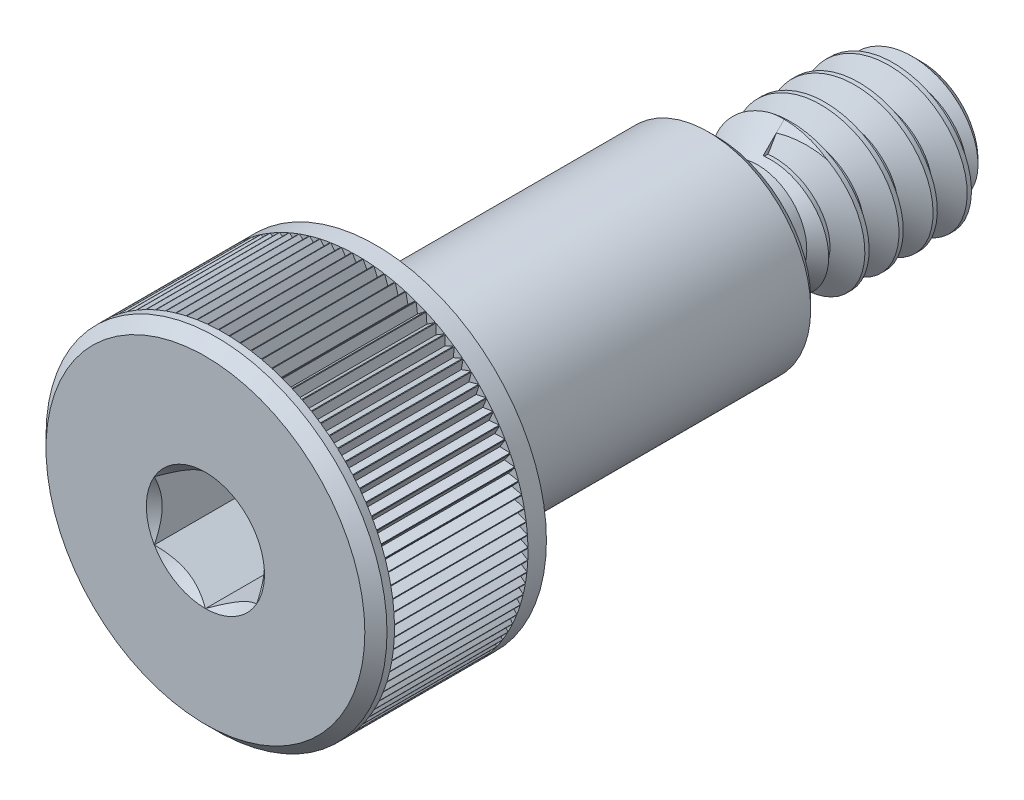
SolidWorks part; units mm, degrees
other "DetailItem1"
other "DetailItem2"
other "DetailItem5"
other "DetailItem6"
ref_plane "Front" through (0, 0, 0) normal (0, 0, 1) x (1, 0, 0)
ref_plane "Top" through (0, 0, 0) normal (0, 1, 0) x (1, 0, 0)
ref_plane "Right" through (0, 0, 0) normal (1, 0, 0) x (0, 0, -1)
sketch "Sketch1" plane through (0, 0, 0) normal (1, 0, 0) x (0, 0, -1)
  line L0 (0, 3.9687) -> (3.9687, 3.9688) construction
  line L1 (3.9687, 3.9688) -> (3.9687, 2.1828) construction
  line L2 (4.9609, 2.3812) -> (11.9062, 2.3812) construction
  line L3 (4.9609, -2.3812) -> (11.9063, -2.3813) construction
  line L4 (11.9063, 1.7526) -> (16.6688, 1.7526) construction
  line L5 (16.6688, 1.7526) -> (16.6688, 0) construction
  line L6 (11.9063, 0) -> (0, 0) construction
  line L7 (0, 0) -> (0, 3.9687) construction
  line L8 (0, 3.9687) -> (0, -3.9688) construction
  line L9 (16.6688, 1.7526) -> (16.6688, -1.7526) construction
  line L10 (11.9062, 2.3812) -> (11.9063, -2.3813) construction
  line L11 (16.6688, -1.7526) -> (14.991, -1.7526) construction
  line L12 (11.9062, 2.3812) -> (11.9063, 0) construction
  line L13 (3.9687, 2.1828) -> (4.7625, 2.1828) construction
  line L14 (4.7625, 2.1828) -> (4.9609, 2.3812) construction
  line L15 (16.6688, 0) -> (11.9063, 0) construction
  line L16 (4.7625, -2.1828) -> (4.9609, -2.3812) construction
  line L17 (3.9688, -2.1828) -> (4.7625, -2.1828) construction
  line L18 (0, -3.9688) -> (3.9688, -3.9688) construction
  line L19 (3.9688, -3.9688) -> (3.9688, -2.1828) construction
  line L20 (16.6688, 2.3813) -> (15.4781, 2.3813) construction
  line L21 (16.6688, -2.3812) -> (15.4781, -2.3812) construction
  line L22 (16.6688, 0) -> (21.4313, 0) construction
  line L23 (7.9375, 0) -> (7.9375, 3.9688) construction
  line L24 (16.6688, -2.3812) -> (16.6688, 2.3813) construction
  line L25 (0, -1.1906) -> (0, 1.1906) construction
  line L26 (16.6191, 1.8385) -> (17.4129, 1.8385) construction
  line L27 (17.4129, 1.8385) -> (17.016, 1.1511) construction
  line L28 (17.016, 1.1511) -> (16.6191, 1.8385) construction
  line L29 (17.016, 1.1511) -> (17.016, 1.237) construction
  line L30 (17.016, 1.8385) -> (17.016, 1.7526) construction
  line L31 (17.3633, 1.7526) -> (16.6688, 1.7526) construction
  line L32 (16.9664, 1.237) -> (17.0656, 1.237) construction
  line L33 (17.016, 1.7956) -> (17.3881, 1.7956) construction
  line L34 (17.016, 1.7956) -> (16.6439, 1.7956) construction
  line L35 (4.9609, 2.3812) -> (4.9609, -2.3812) construction
  line L36 (11.7078, 2.3813) -> (11.9063, 2.1828) construction
  line L37 (11.7078, 2.3813) -> (11.7078, 0) construction
  point P2 (4.1672, 0)
  point P8 (15.4781, -1.7526)
  point P12 (11.9063, 0)
  point P15 (11.7078, 0)
  point P31 (4.5442, 0)
  point P32 (11.3308, 0)
  point P34 (16.6688, 0)
  point P37 (0, 0)
  dimension "Head Dia" = 7.9375
  dimension "Head Ht" = 3.9688
  dimension "Thread Lg" = 4.7625
  dimension "Thread Dia" = 3.5052
  dimension "Shoulder Dia" = 4.7625
  dimension "D1" = 1.1906
  dimension "D2" = 1.6778
  dimension "D3" = 135
  dimension "D4" = 0.7937
  dimension "D5" = 0.1984
  dimension "D6" = 3.9688
  dimension "D7" = 7.5406
  dimension "D8" = 6.7866
  dimension "Hex" = 2.3813
  dimension "Pitch" = 0.7937
  dimension "D9" = 0.0992
  dimension "Shoulder Lg" = 7.9375
  dimension "D10" = 45
sketch "Sketch13" plane through (0, 0, 0) normal (1, 0, 0) x (0, 0, -1)
  line L0 (0, 0) -> (0, 3.9687)
  line L1 (0, 3.9687) -> (3.9687, 3.9688)
  line L2 (3.9687, 3.9688) -> (3.9687, 2.1828)
  line L3 (3.9687, 2.1828) -> (4.7625, 2.1828)
  line L4 (11.9062, 0) -> (11.9062, 2.1828)
  line L5 (4.7625, 2.1828) -> (4.9609, 2.3812)
  line L7 (11.9062, 2.3812) -> (11.9062, 0) construction
  line L8 (11.9062, 2.3812) -> (11.9063, -2.3813) construction
  line L9 (11.9062, 0) -> (0, 0) construction
  line L10 (11.9062, 2.1828) -> (11.7078, 2.3812)
  line L12 (4.9609, 2.3812) -> (11.7078, 2.3812)
  line L13 (0, 0) -> (11.9062, 0)
  line L14 (4.9609, 2.3812) -> (11.9062, 2.3812) construction
  line L18 (16.6688, 2.3813) -> (16.6688, -2.3812) construction
  dimension "D1" = 7.9375
  dimension "D2" = 45
  dimension "D3" = 4.7625
revolve "Revolve1" add sketch "Sketch13" angle 360 about L9
sketch "Sketch12" plane through (0, 0, -11.9062) normal (0, 0, -1) x (-1, 0, 0)
  circle A0 centre (0, 0) radius 1.7526
extrude "Boss-Extrude1" add sketch "Sketch12" along normal up to vertex (4.7625 mm away) up to point (0, 0, -16.6688)
ref_plane "Plane1" through (0, 0, -16.6688) normal (0, 0, 1) x (1, 0, 0)
sketch "Sketch3" plane through (0, 0, -16.6688) normal (0, 0, 1) x (1, 0, 0)
  circle A0 centre (0, 0) radius 1.7526
sketch "Sketch5" plane through (0, 0, 0) normal (1, 0, 0) x (0, 0, -1)
  line L0 (11.9062, 1.7526) -> (13.4722, 1.7526)
  line L1 (13.4722, 1.7526) -> (12.8588, 1.1392)
  line L2 (12.8588, 1.1392) -> (11.9062, 1.1392)
  line L3 (11.9062, 1.7526) -> (11.9062, 1.1392)
  line L4 (11.9063, 1.7526) -> (16.6688, 1.7526) construction
  line L5 (11.9062, 2.3812) -> (11.9062, 0) construction
  line L6 (11.9062, 2.3812) -> (11.9062, -2.3813) construction
  line L7 (16.6688, 0) -> (11.9063, 0) construction
  line L8 (16.6688, -1.7526) -> (16.6688, 1.7526) construction
  dimension "D4" = 0.9525
  dimension "D1" = 45
  dimension "D2" = 3.81
  dimension "D3" = 1.1392
revolve "Cut-Revolve1" cut sketch "Sketch5" angle 360 mid plane about L6
chamfer "Chamfer1" distance 0.4381 angle 45 1 edges at (-1.7526, 0, -16.6688)
chamfer "Chamfer2" distance 0.258 angle 45 1 edges at (-3.9687, 0, 0)
fillet "Fillet1" radius 0.1984 1 edges at (0, 1.1392, -11.9062)
sketch "Sketch10" plane through (0, 0, 0) normal (1, 0, 0) x (0, 0, -1)
  line L0 (0.258, 0) -> (3.7108, 0) construction
  line L1 (3.9687, -3.9688) -> (3.9687, 3.9688) construction
  line L2 (0.258, -3.9687) -> (0.258, 3.9687) construction
  line L3 (0.258, 0) -> (0, 0) construction
  line L4 (3.7108, 0) -> (3.9687, 0) construction
  point P6 (1.9844, 0)
  dimension "D1" = 3.4528
ref_plane "Plane2" through (0, 0, -1.9844) normal (0, 0, 1) x (1, 0, 0)
sketch "Sketch8" plane through (0, 0, 0) normal (0, 0, 1) x (1, 0, 0)
  line L1 (1.1906, 0.6874) -> (0, 1.3748)
  line L2 (0, 1.3748) -> (-1.1906, 0.6874)
  line L3 (-1.1906, 0.6874) -> (-1.1906, -0.6874)
  line L4 (-1.1906, -0.6874) -> (0, -1.3748)
  line L5 (0, -1.3748) -> (1.1906, -0.6874)
  line L6 (1.1906, -0.6874) -> (1.1906, 0.6874)
  circle A0 centre (0, 0) radius 1.1906 construction
extrude "Cut-Extrude2" cut sketch "Sketch8" against normal blind 1.9844
sketch "Sketch9" plane through (0, 0, 0) normal (0, 0, 1) x (1, 0, 0)
  circle A0 centre (0, 0) radius 1.3748
extrude "Cut-Extrude4" cut sketch "Sketch9" against normal blind 1.9844 draft 45
sketch "Sketch16" plane through (0, 0, 0) normal (0, 1, 0) x (1, 0, 0)
  line L0 (0, 7.9375) -> (-2.3812, 7.9375) construction
  line L1 (-2.3812, 11.7078) -> (-2.3812, 4.9609) construction
  line L2 (0, 11.3308) -> (-2.3812, 11.3308) construction
  line L3 (0, 7.9375) -> (0, 11.3308) construction
  line L4 (0, 9.6341) -> (0, 11.3308) construction
  line L5 (0, 11.3308) -> (0, 10.4825) construction
  line L6 (0, 10.4825) -> (-2.3812, 10.4825) construction
  line L7 (0, 4.9609) -> (-2.3812, 4.9609) construction
  line L8 (-2.3812, 4.9609) -> (2.3812, 4.9609) construction
  line L9 (0, 11.9063) -> (2.3812, 11.9063) construction
  point P0 (0, 7.9375)
  point P2 (0, 11.3308)
  point P11 (0, 4.9609)
sketch "reference 1" plane through (0, 0, -3.9687) normal (0, 0, -1) x (-1, 0, 0)
  circle A1 centre (0, 0) radius 3.9687
ref_axis "Center Axis 1" through (0, 0, -4.9609) along (0, 0, -1)
ref_plane "Contact Plane 1" through (0, 0, -16.6688) normal (0, 0, -1) x (-1, 0, 0)
ref_plane "Contact Plane 2" through (0, 0, -3.9687) normal (0, 0, -1) x (-1, 0, 0)
ref_plane "Plane3" through (0, 0, -11.9063) normal (0, 0, 1) x (1, 0, 0)
split "Split1" trim tools "Plane3" bodies to split 118 resulting bodies 127 128
sketch "Sketch15" plane through (0, 0, -16.6688) normal (0, 0, -1) x (-1, 0, 0)
  circle A0 centre (0, 0) radius 1.7526
curve "Helix/Spiral1" pitch 0.7937 height 3.9688 radius 1.7526 centre (0, 0, -16.6688) axis (0, 0, 1) start towards (0, 1, 0)
sketch "Sketch4" plane through (0, 0, 0) normal (1, 0, 0) x (0, 0, -1)
  line L0 (16.9664, 1.237) -> (17.0656, 1.237) construction
  line L1 (17.4129, 1.8385) -> (17.016, 1.1511) construction
  line L3 (17.016, 1.7956) -> (17.3881, 1.7956) construction
  line L4 (17.016, 1.7956) -> (16.6439, 1.7956) construction
  line L5 (17.016, 1.1511) -> (16.6191, 1.8385) construction
  line L6 (16.9664, 1.237) -> (17.0656, 1.237)
  line L7 (17.3881, 1.7956) -> (17.0656, 1.237)
  line L8 (17.016, 1.7956) -> (17.3881, 1.7956)
  line L9 (17.016, 1.7956) -> (16.6439, 1.7956)
  line L10 (16.9664, 1.237) -> (16.6439, 1.7956)
sweep "Cut-Sweep1" cut profiles "Sketch4" path "Helix/Spiral1" align with end faces yes
sketch "Sketch14" plane through (0, 0, -11.9062) normal (0, 0, -1) x (-1, 0, 0)
  line L0 (0, -2.3812) -> (0, 2.3813) construction
  circle A0 centre (0, 0) radius 0.8763
  dimension "D1" = 1.7526
extrude "Boss-Extrude2" add sketch "Sketch14" along normal up to vertex (3.5719 mm away) up to point (0, 2.3813, -15.4781)
sketch "Sketch11" plane through (0, 0, -1.9844) normal (0, 0, 1) x (1, 0, 0)
  line L0 (0, 3.7624) -> (0, 3.9687) construction
  line L1 (0, 3.7624) -> (0.1192, 3.9687)
  line L2 (0, 3.7624) -> (-0.1192, 3.9687)
  line L3 (-0.1192, 3.9687) -> (0.1192, 3.9687)
  line L4 (0, 0) -> (-0.1192, 3.9687) construction
  line L5 (0.1192, 3.9687) -> (0, 0) construction
  circle A2 centre (0, 0) radius 3.9687 construction
  point P8 (2.3908, 0.7309)
  dimension "D1" = 0.2064
  dimension "D2" = 3.439
extrude "Cut-Extrude5" cut sketch "Sketch11" along normal blind 1.5538 and the other way blind 1.5538
pattern_circular "CirPattern1" count 99 over 360 about axis through (0, 0, -11.9063) along (0, 0, 1) of "Cut-Extrude5" reverse direction yes
equation "\"D1@Chamfer1\" = \"Thread Dia@Sketch1\" * .125"
equation "\"D1@Cut-Extrude2\"= \"Head Ht@Sketch1\" * .5"
equation "\"D1@Cut-Extrude4\" = \"D1@Cut-Extrude2\""
equation "\"D1@Chamfer2\"=\"Head Dia@Sketch1\" * .0325"
equation "\"D1@Sketch1\"=\"Pitch@Sketch1\"*1.5"
equation "\"D1@Sketch11\"=\"D1@Chamfer2\"*.8"
equation "\"D4@Sketch5\"=\"Thread Lg@Sketch1\"*0.2"
equation "\"D3@Sketch5\"=(\"Thread Dia@Sketch1\"*0.65)/2"
equation "\"D1@Fillet1\"=\"Pitch@Sketch1\"*.25"
equation "\"D1@Cut-Extrude5\"=\"D1@Sketch10\"*.45"
equation "\"D1@CirPattern1\"=(360/(\"D2@Sketch11\"))-6"
equation "\"D4@Sketch1\"=\"Head Ht@Sketch1\"*0.2"
equation "\"D5@Sketch1\"=\"Head Dia@Sketch1\"*0.025"
equation "\"D6@Sketch1\"=\"Shoulder Lg@Sketch1\"/2"
equation "\"D7@Sketch1\"=\"Shoulder Lg@Sketch1\"*0.95"
equation "\"D8@Sketch1\"=\"D7@Sketch1\"*0.9"
equation "\"D2@Cut-Extrude5\"=\"D1@Sketch10\"*.45"
equation "\"D9@Sketch1\"=\"Pitch@Sketch1\"/8"
equation "\"D1@Sketch14\"=\"Thread Dia@Sketch1\"*.5"
equation "\"D4@Helix/Spiral1\"=\"Pitch@Sketch1\""
equation "\"D3@Helix/Spiral1\"=\"Thread Lg@Sketch1\"-\"Pitch@Sketch1\""
